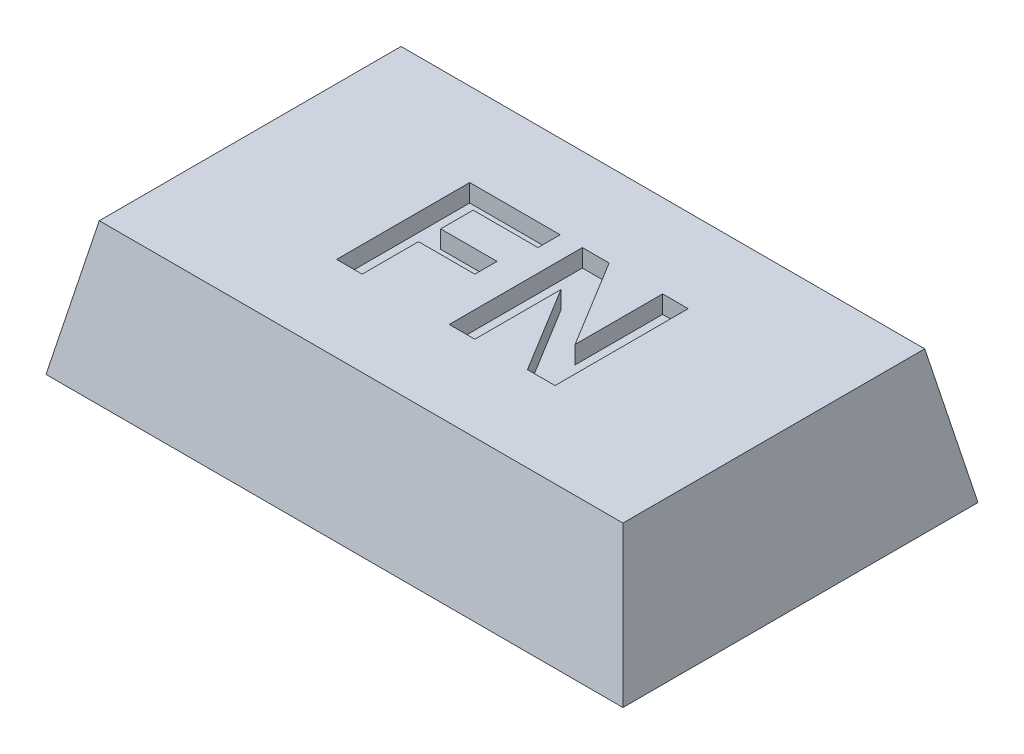
SolidWorks part; units mm, degrees
ref_plane "Front Plane" through (0, 0, 0) normal (0, 0, 1) x (1, 0, 0)
ref_plane "Top Plane" through (0, 0, 0) normal (0, 1, 0) x (1, 0, 0)
ref_plane "Right Plane" through (0, 0, 0) normal (1, 0, 0) x (0, 0, -1)
sketch "Sketch1" plane through (0, 0, 0) normal (0, 1, 0) x (1, 0, 0)
  line L1 (0, 0) -> (13, 0)
  line L2 (0, 0) -> (0, 8)
  line L3 (0, 8) -> (13, 8)
  line L4 (13, 0) -> (13, 8)
  dimension "D1" = 8
  dimension "D2" = 13
extrude "Boss-Extrude1" add sketch "Sketch1" along normal blind 3
sketch "Sketch2" plane through (0, 0, 0) normal (0, 0, 1) x (1, 0, 0)
  line L0 (0, 0) -> (0.6, 3)
  line L1 (0, 3) -> (13, 3) construction
  line L2 (0.6, 3) -> (0, 3)
  line L3 (0, 3) -> (0, 0)
  line L4 (13, 0) -> (12.4, 3)
  line L5 (12.4, 3) -> (13, 3)
  line L6 (13, 3) -> (13, 0)
  dimension "D1" = 0.6
  dimension "D2" = 0.6
extrude "Cut-Extrude1" cut sketch "Sketch2" against normal through all both and the other way through all
sketch "Sketch3" plane through (0, 0, 0) normal (1, 0, 0) x (0, 0, -1)
  line L0 (0, 0) -> (0.6, 3)
  line L1 (8, 3) -> (0, 3) construction
  line L2 (0.6, 3) -> (0, 3)
  line L3 (0, 3) -> (0, 0)
  line L4 (8, 3) -> (7.4, 3)
  line L5 (7.4, 3) -> (8, 0)
  line L6 (8, 3) -> (8, 0)
  dimension "D1" = 0.6
  dimension "D2" = 0.6
extrude "Cut-Extrude2" cut sketch "Sketch3" along normal through all both and the other way through all
sketch "Sketch4" plane through (0, 0, 0) normal (0, -1, 0) x (1, 0, 0)
  line L1 (6.5, 0) -> (6.5, -8) construction
  line L2 (13, -8) -> (0, -8) construction
  line L3 (0, 0) -> (13, 0) construction
  circle A0 centre (6.5, -3.75) radius 1.75
  dimension "D1" = 3.5
  dimension "D2" = 0
  dimension "D3" = 3.75
extrude "Cut-Extrude3" cut sketch "Sketch4" against normal blind 0.4
sketch "Sketch5" plane through (0, 0, 0) normal (0, -1, 0) x (1, 0, 0)
  line L5 (0, 0) -> (13, 0) construction
  line L6 (2.5, -8) -> (10.5, -8)
  line L7 (2.5, -8) -> (2.5, -6.9)
  line L8 (2.5, -6.9) -> (10.5, -6.9)
  line L9 (10.5, -8) -> (10.5, -6.9)
  point P2 (6.5, 0)
  dimension "D1" = 1.1
  dimension "D2" = 4
  dimension "D3" = 4
extrude "Boss-Extrude2" add sketch "Sketch5" along normal blind 2
fillet "Fillet1" radius 4 2 edges at (10.5, -2, -7.45) (2.5, -2, -7.45)
sketch "Sketch6" plane through (0, 3, 0) normal (0, 1, 0) x (1, 0, 0)
  text T0 "FN" font "Arial" height 3
extrude "Cut-Extrude4" cut sketch "Sketch6" against normal blind 0.4
